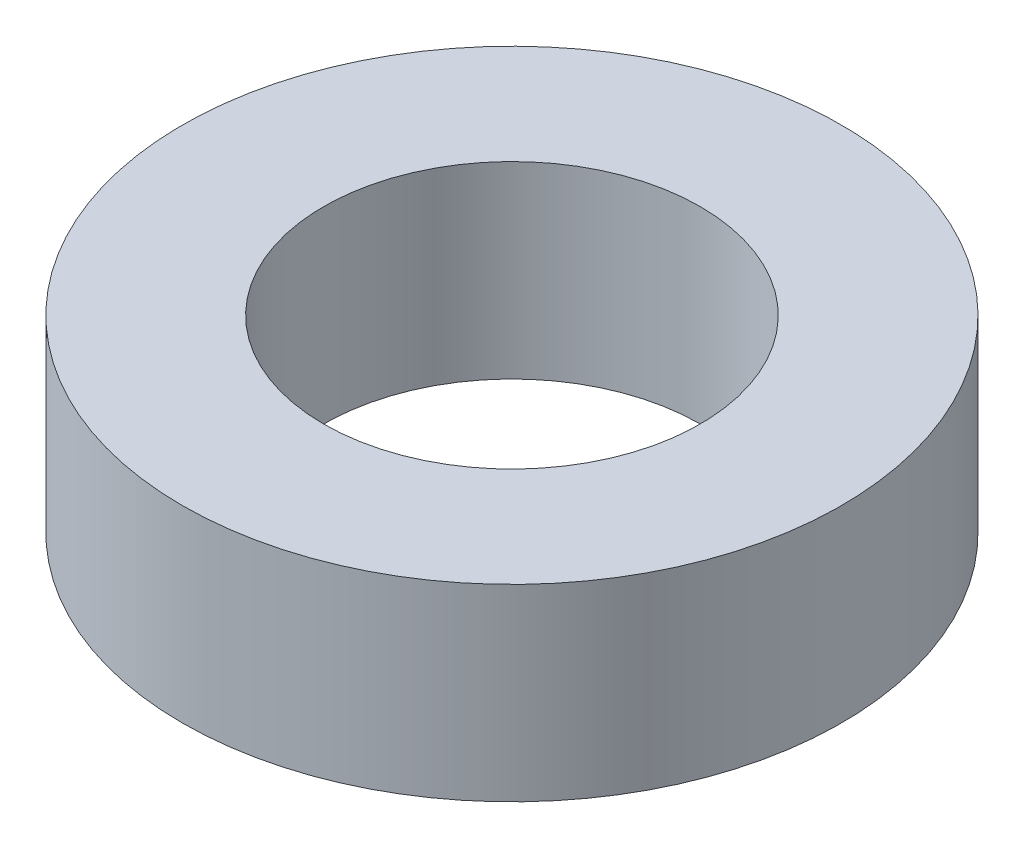
SolidWorks part; units mm, degrees
ref_plane "Front Plane" through (0, 0, 0) normal (0, 0, 1) x (1, 0, 0)
ref_plane "Top Plane" through (0, 0, 0) normal (0, 1, 0) x (1, 0, 0)
ref_plane "Right Plane" through (0, 0, 0) normal (1, 0, 0) x (0, 0, -1)
sketch "Sketch1" plane through (0, 0, 0) normal (0, 1, 0) x (1, 0, 0)
  circle A0 centre (0, 0) radius 17.5
  dimension "FLANGE_OD" = 35
extrude "Boss-Extrude1" add sketch "Sketch1" along normal blind 10
sketch "Sketch2" plane through (0, 0, 0) normal (0, 1, 0) x (1, 0, 0)
  circle A0 centre (0, 0) radius 10
  dimension "BORE_D" = 20
extrude "Cut-Extrude1" cut sketch "Sketch2" along normal through all
sketch "Sketch3" plane through (0, 10, 0) normal (0, 1, 0) x (1, 0, 0)
  circle A0 centre (0, 0) radius 6.5793 construction
  circle A1 centre (-6.5793, 0) radius 1.5
  dimension "BOLT_D" = 3
  dimension "BOLT_PCD" = 13.1585
extrude "Cut-Extrude2" cut sketch "Sketch3" against normal blind 9.0397 rebuild error yes
pattern_circular "CirPattern1" count 8 over 360 rebuild error yes
